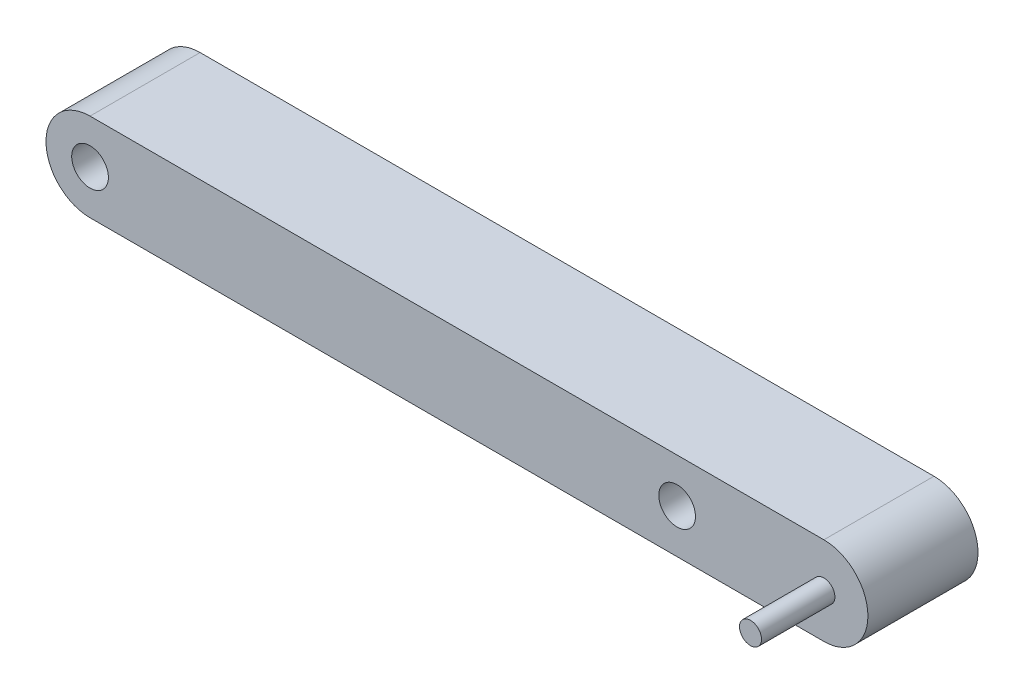
SolidWorks part; units mm, degrees
ref_plane "Alzado" through (0, 0, 0) normal (0, 0, 1) x (1, 0, 0)
ref_plane "Planta" through (0, 0, 0) normal (0, 1, 0) x (1, 0, 0)
ref_plane "Vista lateral" through (0, 0, 0) normal (1, 0, 0) x (0, 0, -1)
sketch "Croquis1" plane through (0, 0, 0) normal (0, 0, 1) x (1, 0, 0)
  line L0 (0, 0) -> (100, 0) construction
  line L1 (0, 6) -> (100, 6)
  line L2 (0, -6) -> (100, -6)
  arc A0 (0, 6) -> (0, -6) centre (0, 0) ccw
  arc A1 (100, -6) -> (100, 6) centre (100, 0) ccw
  circle A2 centre (0, 0) radius 2.5
  circle A3 centre (80, 0) radius 2.5
  circle A4 centre (100, 0) radius 1.5
  point P3 (50, 0)
  dimension "D3" = 5
  dimension "D5" = 5
  dimension "D6" = 3
  dimension "D1" = 100
  dimension "D2" = 12
  dimension "D4" = 20
extrude "Saliente-Extruir2" add sketch "Croquis1" along normal blind 15
extrude "Saliente-Extruir3" add sketch "Croquis1<2>" along normal blind 25 separate body contours A4
sketch "Croquis1<2>" plane through (0, 0, 0) normal (0, 0, 1) x (1, 0, 0) same geometry as "Croquis1"
